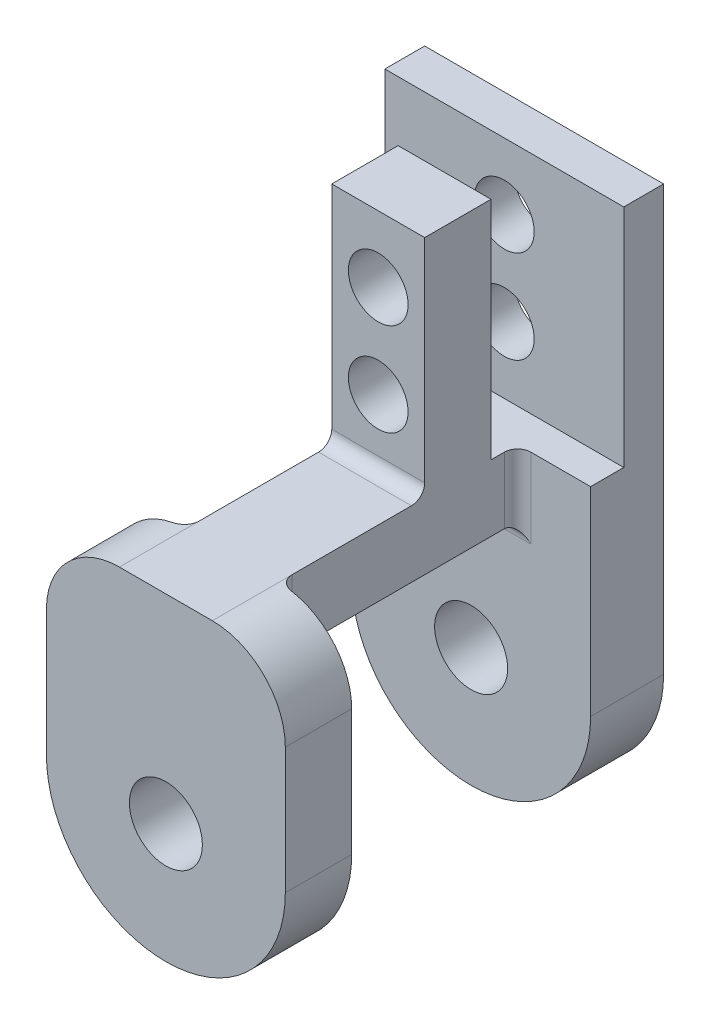
SolidWorks part; units mm, degrees
ref_plane "Plan de face" through (0, 0, 0) normal (0, 0, 1) x (1, 0, 0)
ref_plane "Plan de dessus" through (0, 0, 0) normal (0, 1, 0) x (1, 0, 0)
ref_plane "Plan de droite" through (0, 0, 0) normal (1, 0, 0) x (0, 0, -1)
sketch "Esquisse1" plane through (0, 0, 0) normal (0, 0, 1) x (1, 0, 0)
  line L0 (0, 17) -> (20, 17)
  line L1 (0, 0) -> (20, 0)
  line L2 (0, 0) -> (0, 25.6902)
  line L3 (0, 25.6902) -> (20, 25.6902)
  line L4 (20, 0) -> (20, 25.6902)
  circle A0 centre (10, 5) radius 2.1
  circle A1 centre (10, 12) radius 2.1
  dimension "D2" = 4.2
  dimension "D3" = 4.2
  dimension "D1" = 20
  dimension "D5" = 10
  dimension "D6" = 5
  dimension "D7" = 7
  dimension "D9" = 17
  dimension "D11" = 10
extrude "Boss.-Extru.1" add sketch "Esquisse1" along normal blind 5 contours L1 L4 L0 L2 A1 A0 region at (10, 8.5, 0)
sketch "Esquisse2" plane through (0, 0, 0) normal (0, -1, 0) x (1, 0, 0)
  line L0 (20, 5) -> (20, 0) construction
  line L1 (0, 0) -> (20, 0)
  line L2 (0, 0) -> (0, 5)
  line L3 (0, 5) -> (20, 5)
  line L4 (20, 0) -> (20, 5)
  line L5 (1, 5) -> (1, 0)
  line L6 (19, 5) -> (19, 0)
  line L7 (1, 3) -> (19, 3)
  line L9 (1, 0) -> (19, 0)
  line L10 (1, 0) -> (1, -5)
  line L11 (1, -5) -> (19, -5)
  line L12 (19, 0) -> (19, -5)
  line L13 (1, 0) -> (19, 0)
  line L14 (1, 0) -> (1, -2)
  line L15 (1, -2) -> (19, -2)
  line L16 (19, 0) -> (19, -2)
  point P11 (19, 2.5)
  dimension "D1" = 5
  dimension "D2" = 18
  dimension "D3" = 1
  dimension "D4" = 3
  dimension "D5" = 5
  dimension "D6" = 2
extrude "Boss.-Extru.3" add sketch "Esquisse2" along normal blind 24 contours L15 L10 L11 L12 region at (10, 0, -3.5)
sketch "Esquisse5" plane through (0, 0, 5) normal (0, 0, 1) x (1, 0, 0)
  line L0 (13.5, 17) -> (13.5, 0)
  line L1 (0, 17) -> (20, 17) construction
  line L2 (0, 0) -> (20, 0) construction
  line L3 (13.5, 0) -> (20, 0)
  line L4 (20, 0) -> (20, 17)
  line L5 (20, 0) -> (20, 17) construction
  line L6 (20, 17) -> (13.5, 17)
  line L8 (0, 0) -> (6.5, 0)
  line L9 (0, 0) -> (0, 17)
  line L10 (0, 17) -> (6.5, 17)
  line L11 (6.5, 0) -> (6.5, 17)
  dimension "D1" = 6.5
  dimension "D2" = 6.5
extrude "Enlèv. mat.-Extru.3" cut sketch "Esquisse5" against normal blind 18
sketch "Esquisse10" plane through (0, 0, 5) normal (0, 0, 1) x (1, 0, 0)
  line L1 (6.5, 0) -> (13.5, 0)
  line L2 (6.5, 0) -> (6.5, -3)
  line L3 (6.5, -3) -> (13.5, -3)
  line L4 (13.5, 0) -> (13.5, -3)
  dimension "D1" = 7
  dimension "D2" = 3
extrude "Boss.-Extru.6" add sketch "Esquisse10" against normal blind 10
sketch "Esquisse11" plane through (0, 0, 0) normal (0, 1, 0) x (1, 0, 0)
  line L0 (6.5, 2) -> (6.5, 0) construction
  line L1 (6.5, 0) -> (13.5, 0)
  line L2 (6.5, 0) -> (6.5, 5)
  line L3 (6.5, 5) -> (13.5, 5)
  line L4 (13.5, 0) -> (13.5, 5)
  line L5 (6.5, 0) -> (13.5, 0) construction
  line L6 (1, 5) -> (19, 5) construction
  line L8 (13.5, 4.5) -> (6.5, 4.5)
  line L9 (13.5, 4.5) -> (13.5, 0)
  line L10 (13.5, 0) -> (6.5, 0)
  line L11 (6.5, 4.5) -> (6.5, 0)
  line L12 (6.5, 4.5) -> (13.5, 4.5)
  line L13 (6.5, 4.5) -> (6.5, 7.5)
  line L14 (6.5, 7.5) -> (13.5, 7.5)
  line L15 (13.5, 4.5) -> (13.5, 7.5)
  line L16 (6.5, 4.5) -> (1, 4.5)
  line L17 (6.5, 4.5) -> (6.5, 7.5)
  line L18 (6.5, 7.5) -> (1, 7.5)
  line L19 (1, 4.5) -> (1, 7.5)
  line L20 (13.5, 4.5) -> (19, 4.5)
  line L21 (13.5, 4.5) -> (13.5, 7.5)
  line L22 (13.5, 7.5) -> (19, 7.5)
  line L23 (19, 4.5) -> (19, 7.5)
  line M12 (19, 2) -> (19, 5)
  line M13 (19, 5) -> (1, 5)
  line M14 (1, 5) -> (1, 2)
  dimension "D1" = 7
  dimension "D2" = 4.5
  dimension "D3" = 3
  dimension "D4" = 5.5
  dimension "D5" = 5.5
extrude "Boss.-Extru.7" add sketch "Esquisse11" along normal blind 17 contours L19 L13 L18 M13 | L15 L14 L13 M13 | L23 L22 L15 M13 | L16 L2 M13 M14 | L8 L4 L2 M13 | L4 L20 M12 M13 region at (3.75, 0, -4.75) region at (10, 0, -4.75) region at (16.25, 0, -4.75) region at (10, 0, -6.25) region at (3.75, 0, -6.25) region at (16.25, 0, -6.25)
sketch "Esquisse12" plane through (0, 0, 0) normal (0, -1, 0) x (1, 0, 0)
  line L5 (1, -5) -> (19, -5)
  line L6 (1, -5) -> (1, -7.5)
  line L7 (1, -7.5) -> (19, -7.5)
  line L8 (19, -5) -> (19, -7.5)
extrude "Boss.-Extru.8" add sketch "Esquisse12" along normal blind 24
fillet "Congé3" radius 9 2 edges at (19, -24, -4.75) (1, -24, -4.75)
sketch "Esquisse20" plane through (0, 0, 5) normal (0, 0, 1) x (1, 0, 0)
  circle A0 centre (10, 5) radius 2.25
  circle A1 centre (10, 12) radius 2.25
  dimension "D1" = 4.5
extrude "Enlèv. mat.-Extru.7" cut sketch "Esquisse20" against normal blind 18
sketch "Esquisse22" plane through (0, 0, -2) normal (0, 0, 1) x (1, 0, 0)
  line L1 (13.5, 0) -> (6.5, 0)
  line L2 (13.5, 0) -> (13.5, -5)
  line L3 (13.5, -5) -> (6.5, -5)
  line L4 (6.5, 0) -> (6.5, -5)
  dimension "D1" = 7
  dimension "D2" = 5
extrude "Boss.-Extru.9" add sketch "Esquisse22" along normal blind 23
sketch "Esquisse27" plane through (0, 0, 0) normal (0, 1, 0) x (1, 0, 0)
  line L1 (13.5, -21) -> (1, -21)
  line L2 (13.5, -21) -> (13.5, -16)
  line L3 (13.5, -16) -> (1, -16)
  line L4 (1, -21) -> (1, -16)
  line L5 (13.5, -16) -> (19, -16)
  line L6 (13.5, -16) -> (13.5, -21)
  line L7 (13.5, -21) -> (19, -21)
  line L8 (19, -16) -> (19, -21)
  line M5 (6.5, -5) -> (6.5, -21)
  line M6 (6.5, -21) -> (13.5, -21)
  line M7 (13.5, -21) -> (13.5, -5)
  dimension "D1" = 5
  dimension "D2" = 5
  dimension "D3" = 18
  dimension "D4" = 5.5
extrude "Boss.-Extru.10" add sketch "Esquisse27" against normal blind 24 contours L4 L1 L3 M5 | L8 L5 L7 M7 | L3 M7 M5 M6 region at (10, 0, 18.5) region at (16.25, 0, 18.5) region at (3.75, 0, 18.5)
fillet "Congé4" radius 9 2 edges at (1, -24, 18.5) (19, -24, 18.5)
sketch "Esquisse28" plane through (0, 0, 21) normal (0, 0, 1) x (1, 0, 0)
  line L0 (19, -15) -> (19, 0) construction
  circle A0 centre (10, -15) radius 2.75
  dimension "D1" = 5.5
  dimension "D2" = 9
  dimension "D3" = 9
extrude "Enlèv. mat.-Extru.8" cut sketch "Esquisse28" against normal blind 44
fillet "Congé5" radius 1 7 edges at (10, -5, 16) (10, -5, -2) (13.5, -2.5, 16) (13.5, -2.5, -2) (6.5, -2.5, -2) (6.5, -2.5, 16) (10, 0, 5)
fillet "Congé6" radius 5.5 2 edges at (1, 0, 18.5) (19, 0, 18.5)
